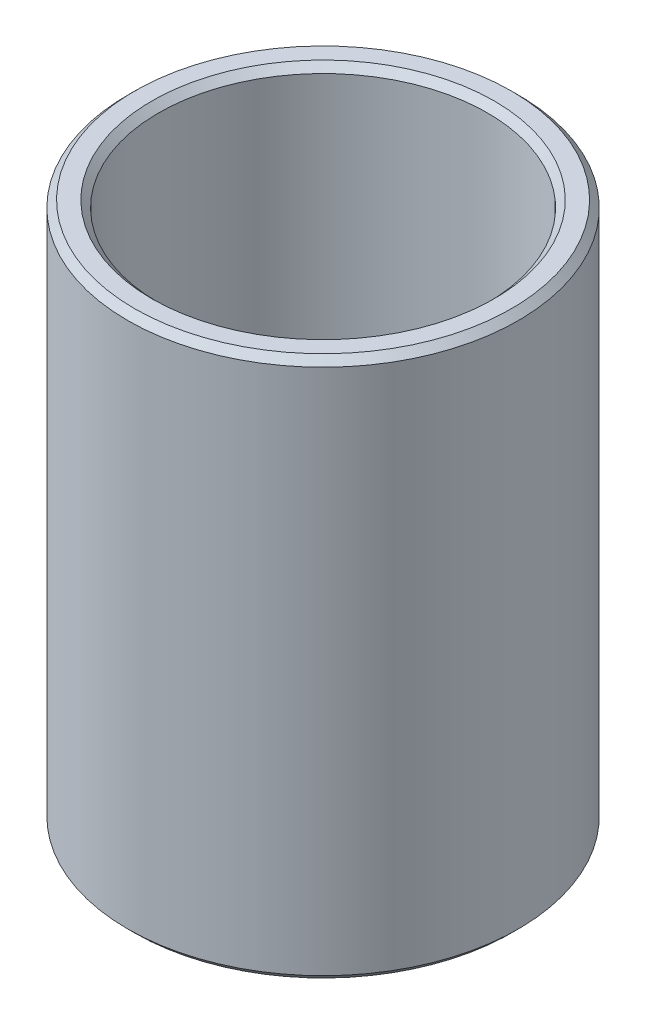
SolidWorks part; units mm, degrees
ref_plane "Front Plane" through (0, 0, 0) normal (0, 0, 1) x (1, 0, 0)
ref_plane "Top Plane" through (0, 0, 0) normal (0, 1, 0) x (1, 0, 0)
ref_plane "Right Plane" through (0, 0, 0) normal (1, 0, 0) x (0, 0, -1)
sketch "Sketch1" plane through (0, 0, 0) normal (0, 1, 0) x (1, 0, 0)
  circle A0 centre (0, 0) radius 37.5
  dimension "SLEEVE_OD" = 75
extrude "Boss-Extrude1" add sketch "Sketch1" along normal blind 103.7969
sketch "Sketch2" plane through (0, 0, 0) normal (0, 1, 0) x (1, 0, 0)
  circle A0 centre (0, 0) radius 31.5655
  dimension "BORE_D" = 63.131
extrude "Cut-Extrude1" cut sketch "Sketch2" along normal through all
chamfer "Chamfer1" distance 1.3165 angle 45 4 edges at (0, 103.7969, 31.5655) (0, 0, 31.5655) (0, 0, 37.5) (0, 103.7969, 37.5)
